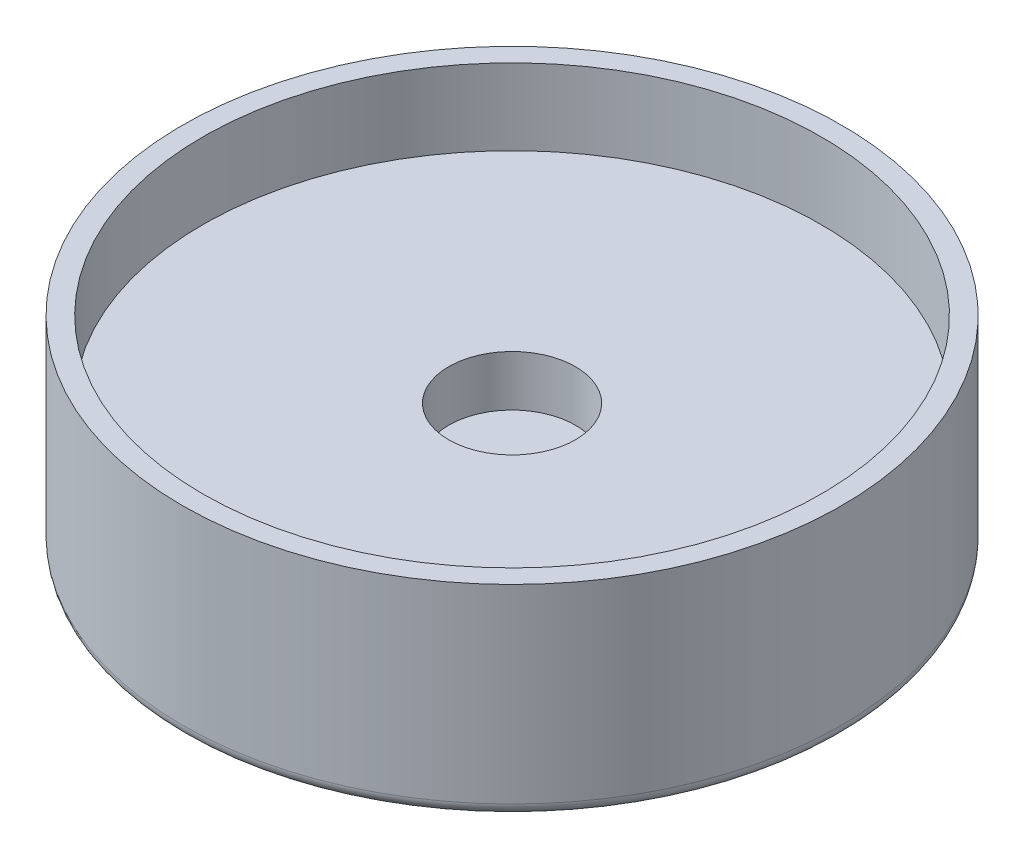
SolidWorks part; units mm, degrees
ref_plane "Front Plane" through (0, 0, 0) normal (0, 0, 1) x (1, 0, 0)
ref_plane "Top Plane" through (0, 0, 0) normal (0, 1, 0) x (1, 0, 0)
ref_plane "Right Plane" through (0, 0, 0) normal (1, 0, 0) x (0, 0, -1)
other "Configuration Table"
sketch "草图1" plane through (0, 0, 0) normal (0, 1, 0) x (1, 0, 0)
  circle A0 centre (0, 0) radius 13
  dimension "D1" = 26
extrude "凸台-拉伸1" add sketch "草图1" along normal blind 8
sketch "草图2" plane through (0, 8, 0) normal (0, 1, 0) x (1, 0, 0)
  circle A0 centre (0, 0) radius 12
  dimension "D1" = 24
extrude "切除-拉伸1" cut sketch "草图2" against normal blind 3
sketch "草图3" plane through (0, 5, 0) normal (0, 1, 0) x (1, 0, 0)
  circle A0 centre (0, 0) radius 2.5
  dimension "D1" = 5
extrude "切除-拉伸2" cut sketch "草图3" against normal blind 2
fillet "圆角1" radius 0.5 1 edges at (0, 0, 13)
sketch "草图4" plane through (0, 5, 0) normal (0, 1, 0) x (1, 0, 0)
  circle A0 centre (0, 0) radius 12.2
  dimension "D1" = 24.4
extrude "切除-拉伸3" cut sketch "草图4" along normal through all
